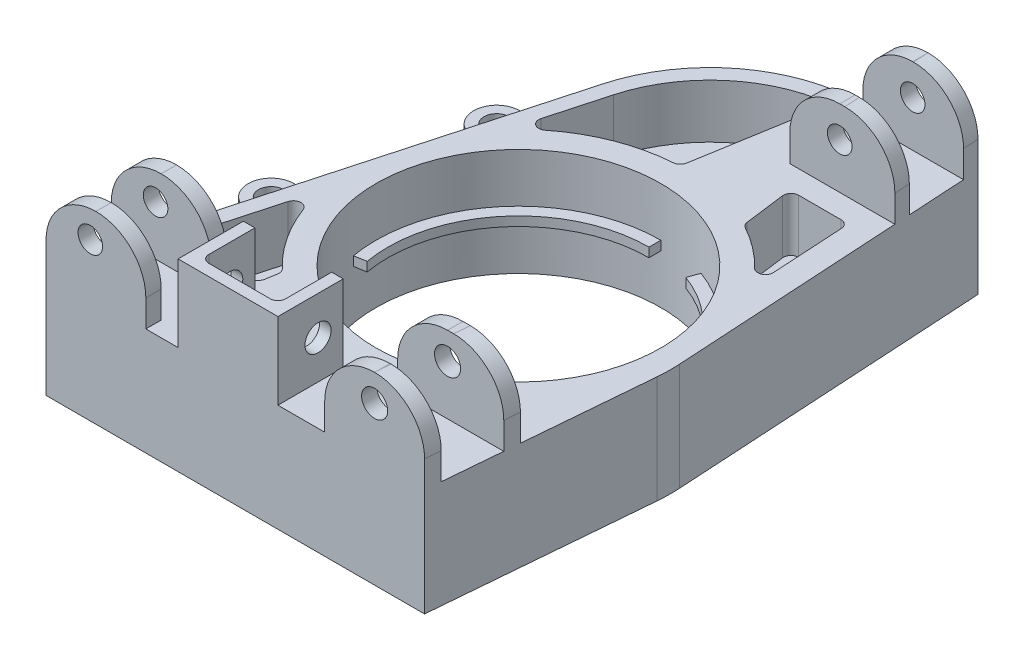
SolidWorks part; units mm, degrees
ref_plane "Front Plane" through (0, 0, 0) normal (0, 0, 1) x (1, 0, 0)
ref_plane "Top Plane" through (0, 0, 0) normal (0, 1, 0) x (1, 0, 0)
ref_plane "Right Plane" through (0, 0, 0) normal (1, 0, 0) x (0, 0, -1)
sketch "Sketch1" plane through (0, 0, 0) normal (0, 1, 0) x (1, 0, 0)
  line L0 (-76.5386, -79.7284) -> (48.6713, -79.7284)
  line L1 (55.0613, -5.2886) -> (48.6713, 103.3395)
  line L2 (48.6713, 103.3395) -> (10.8418, 103.3395)
  line L3 (-38.131, 66.0414) -> (-70.9669, -53.0584)
  line L4 (48.6713, 103.3395) -> (48.6713, -79.7284) construction
  line L5 (48.6713, -79.7284) -> (55.0613, -5.2886)
  line L6 (-76.5386, -79.7284) -> (-76.5386, -53.0584)
  line L7 (-76.5386, -53.0584) -> (-70.9669, -53.0584)
  circle A0 centre (0, 0) radius 47.117
  circle A2 centre (0, 0) radius 120.65
  arc A3 (10.8418, 103.3395) -> (-38.131, 66.0414) centre (10.8418, 52.5395) ccw
  point P10 (0, -47.117)
  point P11 (47.117, 0)
  point P16 (-47.117, 0)
  dimension "D2" = 94.234
  dimension "D3" = 7.62
  dimension "D4" = 8.89
  dimension "D5" = 26.67
  dimension "D1" = 241.3
  dimension "D6" = 50.8
extrude "Base" add sketch "Sketch1" along normal blind 35.56 contours L2 L3 L0 L1 A0 | L1 L4 A0 L5 region at (-74.284, 0, 66.3934)
sketch "Sketch2" plane through (0, 35.56, 0) normal (0, 1, 0) x (1, 0, 0)
  line L0 (48.6713, 103.3395) -> (48.9701, 98.2595)
  line L1 (55.0613, -5.2886) -> (48.6713, 103.3395) construction
  line L2 (48.9701, 98.2595) -> (15.6513, 98.2595)
  line L3 (15.6513, 98.2595) -> (15.6513, 103.3395)
  line L4 (48.6713, 103.3395) -> (10.8418, 103.3395) construction
  line L5 (15.6513, 103.3395) -> (48.6713, 103.3395)
  line L6 (15.6513, -74.6484) -> (49.1074, -74.6484)
  line L7 (49.1074, -74.6484) -> (48.6713, -79.7284)
  line L8 (-76.5386, -79.7284) -> (48.6713, -79.7284) construction
  line L9 (48.6713, -79.7284) -> (15.6513, -79.7284)
  line L10 (15.6513, -79.7284) -> (15.6513, -74.6484)
  line L11 (15.6513, 103.3395) -> (15.6513, -79.7284) construction
  line L12 (48.6713, -79.7284) -> (55.0613, -5.2886) construction
  line L13 (15.6513, 79.2095) -> (15.6513, 74.1295)
  line L14 (15.6513, 74.1295) -> (50.3896, 74.1295)
  line L15 (50.3896, 74.1295) -> (50.0907, 79.2095)
  line L16 (50.0907, 79.2095) -> (15.6513, 79.2095)
  line L17 (-76.5386, -79.7284) -> (-76.5386, -53.0584) construction
  line L18 (15.6513, -50.5184) -> (51.1787, -50.5184)
  line L19 (15.6513, -50.5184) -> (15.6513, -55.5984)
  line L20 (15.6513, -55.5984) -> (50.7427, -55.5984)
  line L21 (51.1787, -50.5184) -> (50.7427, -55.5984)
  line L22 (-43.5186, -53.0584) -> (-76.5386, -53.0584)
  line L23 (-43.5186, -53.0584) -> (-43.5186, -58.1384)
  line L24 (-43.5186, -58.1384) -> (-76.5386, -58.1384)
  line L25 (-76.5386, -53.0584) -> (-76.5386, -58.1384)
  line L26 (-43.5186, -79.7284) -> (-43.5186, -60.0458) construction
  line L27 (-76.5386, -74.6484) -> (-43.5186, -74.6484)
  line L28 (-76.5386, -74.6484) -> (-76.5386, -79.7284)
  line L29 (-76.5386, -79.7284) -> (-43.5186, -79.7284)
  line L30 (-43.5186, -74.6484) -> (-43.5186, -79.7284)
  line L31 (-76.5386, -79.7284) -> (48.6713, -79.7284) construction
  dimension "D1" = 33.02
  dimension "D2" = 5.08
  dimension "D3" = 5.08
  dimension "D4" = 19.05
  dimension "D5" = 5.08
  dimension "D6" = 5.08
  dimension "D7" = 19.05
  dimension "D8" = 33.02
  dimension "D9" = 5.08
  dimension "D10" = 5.08
extrude "A-Arms" add sketch "Sketch2" along normal blind 25.4
fillet "Fillet a-arm tab f" radius 16.51 12 edges at (48.8894, 60.96, 77.1884) (50.9607, 60.96, 53.0584) (15.6513, 60.96, 77.1884) (15.6513, 60.96, 53.0584) (50.2402, 60.96, -76.6695) (48.8207, 60.96, -100.7995) (15.6513, 60.96, -76.6695) (15.6513, 60.96, -100.7995) (-76.5386, 60.96, 77.1884) (-43.5186, 60.96, 77.1884) (-43.5186, 60.96, 55.5984) (-76.5386, 60.96, 55.5984)
fillet "Fillet2" radius 50.8 1 edges at (55.0613, 17.78, 5.2886)
ref_plane "Plane1" through (0, 16, 0) normal (0, -1, 0) x (-1, 0, 0)
sketch "Sketch3" plane through (0, 16, 0) normal (0, -1, 0) x (-1, 0, 0)
  line L0 (42.2021, 51.2753) -> (51.7371, 53.9041)
  line L1 (38.131, 66.0414) -> (70.9669, -53.0584) construction
  line L2 (62.3195, -21.6933) -> (72.1885, -18.9724)
  line L3 (54.0145, 33.5988) -> (63.3923, -0.4157)
  line L4 (42.2021, 51.2753) -> (62.3195, -21.6933)
  circle A0 centre (0, 0) radius 71.12
  circle A1 centre (53.7624, 46.5582) radius 4.191
  circle A2 centre (70.1632, -11.6265) radius 4.191
  arc A3 (56.852, 39.5926) -> (51.7371, 53.9041) centre (53.7624, 46.5582) ccw
  arc A4 (72.1885, -18.9724) -> (69.039, -4.0899) centre (70.1632, -11.6265) ccw
  arc A5 (63.3923, -0.4157) -> (69.039, -4.0899) centre (68.2896, 0.9345) ccw
  arc A6 (54.0145, 33.5988) -> (56.852, 39.5926) centre (58.9118, 34.949) cw
  dimension "D1" = 60.452
  dimension "D2" = 142.24
  dimension "D3" = 8.382
  dimension "D4" = 8.382
  dimension "D5" = 15.24
  dimension "D6" = 15.24
  dimension "D7" = 5.08
extrude "Boss-Extrude3" add sketch "Sketch3" against normal blind 10 contours L3 A6 A3 A0 A1 L0 L4 L2 A2 A4 A5 | A0 A3 L0 A1 | L2 A4 A0 A2 region at (-56.0903, 16, -15.5313) region at (-49.7533, 16, -53.1565) region at (-69.0083, 16, 17.9571)
fillet "Fillet3" radius 12.7 2 edges at (-42.2021, 21, -51.2753) (-62.3195, 21, 21.6933)
sketch "Sketch6" plane through (0, 0, -103.3395) normal (0, 0, -1) x (-1, 0, 0)
  line L0 (-32.1471, 60.96) -> (-32.1471, 40.2979) construction
  circle A1 centre (-32.1471, 50.673) radius 4.064
  dimension "D1" = 15.113
  dimension "D2" = 8.128
extrude "Tab Holes 1" cut sketch "Sketch6" against normal blind 38.1
sketch "Sketch7" plane through (0, 0, 53.0584) normal (0, 0, -1) x (-1, 0, 0)
  line L0 (60.0286, 60.96) -> (60.0286, 35.56) construction
  line L4 (43.5186, 35.56) -> (70.9669, 35.56) construction
  circle A0 centre (61.8814, 51.9657) radius 4.064
  dimension "D1" = 16.51
  dimension "D2" = 8.128
extrude "Tab Holes 2" cut sketch "Sketch7" against normal through all
ref_plane "midplane" through (0, 17.78, 0) normal (0, 1, 0) x (1, 0, 0)
sketch "Sketch8" plane through (0, 17.78, 0) normal (0, 1, 0) x (1, 0, 0)
  line L0 (0, 0) -> (0, 47.117)
  line L1 (0, 0) -> (16.115, 44.2755)
  line L2 (0, 0) -> (30.2862, -36.0937)
  line L3 (0, 0) -> (40.8045, -23.5585)
  line L4 (0, 0) -> (-46.4012, -8.1818)
  line L5 (0, 0) -> (-40.8045, -23.5585)
  circle A0 centre (0, 0) radius 47.117
  circle A1 centre (0, 0) radius 43.18
  circle A2 centre (0, 0) radius 47.117 construction
  point P14 (0, 0)
  dimension "D1" = 20
  dimension "D2" = 3
extrude "mid-feature bearing" add sketch "Sketch8" along normal blind 1.524 and the other way blind 1.524 contours A1 L0 A0 L4 | A1 L5 A0 L2 | A1 L3 A0 L1 region at (-33.6343, 17.78, -28.2226) region at (16.1479, 17.78, -42.1687) region at (28.4423, 17.78, 35.0713)
sketch "Sketch9" plane through (0, 35.56, 0) normal (0, 1, 0) x (1, 0, 0)
  line L0 (-43.5186, -79.7284) -> (15.6513, -79.7284) construction
  line L1 (-32.844, -79.7284) -> (0.176, -79.7284)
  line L2 (-32.844, -79.7284) -> (-32.844, -75.9184)
  line L3 (-32.844, -75.9184) -> (0.176, -75.9184)
  line L4 (0.176, -79.7284) -> (0.176, -75.9184)
  line L5 (-43.5186, -58.1384) -> (15.6513, -58.1384) construction
  line L6 (0.176, -75.9184) -> (-3.634, -75.9184)
  line L7 (0.176, -75.9184) -> (0.176, -58.1384)
  line L8 (0.176, -58.1384) -> (-3.634, -58.1384)
  line L9 (-3.634, -75.9184) -> (-3.634, -58.1384)
  line L10 (-32.844, -75.9184) -> (-29.034, -75.9184)
  line L11 (-32.844, -75.9184) -> (-32.844, -58.1384)
  line L12 (-32.844, -58.1384) -> (-29.034, -58.1384)
  line L13 (-29.034, -75.9184) -> (-29.034, -58.1384)
  line L14 (15.6513, -50.5184) -> (15.6513, -55.5984) construction
  line M30 (-43.5186, -79.7284) -> (15.6513, -79.7284)
  dimension "D1" = 3.81
  dimension "D2" = 3.81
  dimension "D3" = 3.81
  dimension "D4" = 25.4
extrude "Boss-Extrude5" add sketch "Sketch9" along normal blind 25.4 contours L3 L13 L12 L11 | L4 L3 L2 M30 | L9 L3 L7 L8 region at (-16.334, 35.56, 77.8234) region at (-30.939, 35.56, 67.0284) region at (-1.729, 35.56, 67.0284)
fillet "Pushrod Str" radius 2.54 2 edges at (-3.634, 48.26, 75.9184) (-29.034, 48.26, 75.9184)
sketch "Sketch10" plane through (-32.844, 0, 0) normal (-1, 0, 0) x (0, 0, 1)
  line L0 (58.1384, 48.26) -> (80.5175, 48.26) construction
  line L1 (58.1384, 60.96) -> (58.1384, 35.56) construction
  circle A0 centre (66.4613, 48.26) radius 4.318
  dimension "D1" = 8.3229
extrude "Pushrod Holes" cut sketch "Sketch10" against normal through all
mirror "Mirror2" [suppressed] of bodies 108
delete or keep bodies "Body-Delete/Keep 1" [suppressed] type delete bodies bodies 108
sketch "Sketch11" plane through (0, 0, 79.7284) normal (0, 0, -1) x (-1, 0, 0)
  line L0 (-32.1613, 60.96) -> (-32.1613, 35.56) construction
  line L2 (-15.6513, 35.56) -> (-48.6713, 35.56) construction
  line L3 (-48.6713, 44.45) -> (-48.6713, 0) construction
  circle A0 centre (-32.1613, 52.07) radius 4.318
  arc A1 (-15.6513, 44.45) -> (-32.131, 60.96) centre (-32.1613, 44.45) ccw construction
  dimension "D1" = 16.51
extrude "Tab Holes 3" cut sketch "Sketch11" along normal blind 50.8
ref_plane "Plane2" through (0, 0, -88.7345) normal (0, 0, -1) x (-1, 0, 0)
ref_axis "Axis1" through (32.1471, 50.673, -74.1295) along (0, 0, -1)
ref_point "top wishbont att pt"
ref_plane "Plane3" through (0, 0, 65.1234) normal (0, 0, -1) x (-1, 0, 0)
ref_axis "Axis2" through (32.1613, 52.07, 50.5184) along (0, 0, 1)
ref_point "Bottom Wish"
ref_axis "Axis3" through (-61.8814, 51.9657, 58.1384) along (0, 0, -1)
ref_point "Anchor tierod"
sketch "Sketch12" plane through (0, 35.56, 0) normal (0, 1, 0) x (1, 0, 0)
  line L0 (23.2751, 66.5392) -> (42.5844, 66.5392)
  line L1 (42.5844, 66.5392) -> (44.5791, 32.63)
  line L75 (5.2782, 97.9198) -> (-1.916, 55.2118)
  line L76 (22.9504, 69.0495) -> (25.5453, 48.9841)
  line L77 (-38.4386, -47.9784) -> (-37.2318, -40.8143)
  line L106 (-23.954, -70.8384) -> (-8.714, -70.8384)
  line L107 (-8.714, -70.8384) -> (-8.714, -53.0584)
  line L108 (-8.714, -53.0584) -> (5.256, -53.0584)
  line L109 (5.256, -53.0584) -> (5.256, -74.6484)
  line L110 (5.256, -74.6484) -> (10.5713, -74.6484)
  line L111 (10.5713, -74.6484) -> (10.5713, -69.5684)
  line L112 (10.5713, -69.5684) -> (44.4448, -69.5684)
  line L113 (44.4448, -69.5684) -> (45.2079, -60.6784)
  line L114 (45.2079, -60.6784) -> (10.5713, -60.6784)
  line L115 (10.5713, -60.6784) -> (10.5713, -45.4384)
  line L116 (10.5713, -45.4384) -> (46.5161, -45.4384)
  line L117 (46.5161, -45.4384) -> (49.6857, -8.5145)
  line L118 (49.7743, -1.9195) -> (45.5996, 69.0495)
  line L119 (45.5996, 69.0495) -> (10.5713, 69.0495)
  line L120 (10.5713, 69.0495) -> (10.5713, 84.2895)
  line L121 (10.5713, 84.2895) -> (44.7031, 84.2895)
  line L122 (44.7031, 84.2895) -> (44.1802, 93.1795)
  line L123 (44.1802, 93.1795) -> (10.5713, 93.1795)
  line L124 (10.5713, 93.1795) -> (10.5713, 98.2587)
  line L126 (-33.2338, 64.6912) -> (-64.2968, -47.9784)
  line L127 (-64.2968, -47.9784) -> (-38.4386, -47.9784)
  line L128 (-38.4386, -47.9784) -> (-38.4386, -63.2184)
  line L129 (-38.4386, -63.2184) -> (-71.4586, -63.2184)
  line L130 (-71.4586, -63.2184) -> (-71.4586, -69.5684)
  line L131 (-71.4586, -69.5684) -> (-38.4386, -69.5684)
  line L132 (-38.4386, -69.5684) -> (-38.4386, -74.6484)
  line L133 (-38.4386, -74.6484) -> (-37.924, -74.6484)
  line L134 (-37.924, -74.6484) -> (-37.924, -53.0584)
  line L135 (-37.924, -53.0584) -> (-23.954, -53.0584)
  line L136 (-23.954, -53.0584) -> (-23.954, -70.8384)
  line L137 (-23.954, -70.8384) -> (-8.714, -70.8384)
  line L138 (-8.714, -70.8384) -> (-8.714, -53.0584)
  line L139 (-8.714, -53.0584) -> (5.256, -53.0584)
  line L140 (5.256, -53.0584) -> (5.256, -74.6484)
  line L141 (5.256, -74.6484) -> (10.5713, -74.6484)
  line L142 (10.5713, -74.6484) -> (10.5713, -69.5684)
  line L143 (10.5713, -69.5684) -> (44.4448, -69.5684)
  line L144 (44.4448, -69.5684) -> (45.2079, -60.6784)
  line L145 (45.2079, -60.6784) -> (10.5713, -60.6784)
  line L146 (10.5713, -60.6784) -> (10.5713, -45.4384)
  line L147 (10.5713, -45.4384) -> (46.5161, -45.4384)
  line L148 (46.5161, -45.4384) -> (49.6857, -8.5145)
  line L149 (49.7743, -1.9195) -> (45.5996, 69.0495)
  line L150 (45.5996, 69.0495) -> (10.5713, 69.0495)
  line L151 (10.5713, 69.0495) -> (10.5713, 84.2895)
  line L152 (10.5713, 84.2895) -> (44.7031, 84.2895)
  line L153 (44.7031, 84.2895) -> (44.1802, 93.1795)
  line L154 (44.1802, 93.1795) -> (10.5713, 93.1795)
  line L155 (10.5713, 93.1795) -> (10.5713, 98.2587)
  line L157 (-33.2338, 64.6912) -> (-64.2968, -47.9784)
  line L158 (-64.2968, -47.9784) -> (-38.4386, -47.9784)
  line L159 (-38.4386, -47.9784) -> (-38.4386, -63.2184)
  line L160 (-38.4386, -63.2184) -> (-71.4586, -63.2184)
  line L161 (-71.4586, -63.2184) -> (-71.4586, -69.5684)
  line L162 (-71.4586, -69.5684) -> (-38.4386, -69.5684)
  line L163 (-38.4386, -69.5684) -> (-38.4386, -74.6484)
  line L164 (-38.4386, -74.6484) -> (-37.924, -74.6484)
  line L165 (-37.924, -74.6484) -> (-37.924, -53.0584)
  line L166 (-37.924, -53.0584) -> (-23.954, -53.0584)
  line L167 (-23.954, -53.0584) -> (-23.954, -70.8384)
  circle A22 centre (0, 0) radius 55.245
  arc A23 (49.6857, -8.5145) -> (49.7743, -1.9195) centre (4.1332, -4.6043) ccw
  arc A24 (10.5713, 98.2587) -> (-33.2338, 64.6912) centre (10.8418, 52.5395) ccw
  arc A25 (49.6857, -8.5145) -> (49.7743, -1.9195) centre (4.1332, -4.6043) ccw
  arc A26 (10.5713, 98.2587) -> (-33.2338, 64.6912) centre (10.8418, 52.5395) ccw
  dimension "D1" = 5.08
extrude "Cut-Extrude1" cut sketch "Sketch12" against normal blind 17.78 contours L75 A26 L157 A22 | A22 L1 L0 L76 | A22 L157 L158 L77
fillet "Fillet4" radius 2.54 11 edges at (-37.2318, 26.67, 40.8143) (-38.4386, 26.67, 47.9784) (-64.2968, 26.67, 47.9784) (-54.1231, 26.67, 11.077) (-40.8, 26.67, -37.2474) (5.2782, 26.67, -97.9198) (-1.916, 26.67, -55.2118) (25.5453, 26.67, -48.9841) (44.5791, 26.67, -32.63) (42.5844, 26.67, -66.5392) (23.2751, 26.67, -66.5392)
